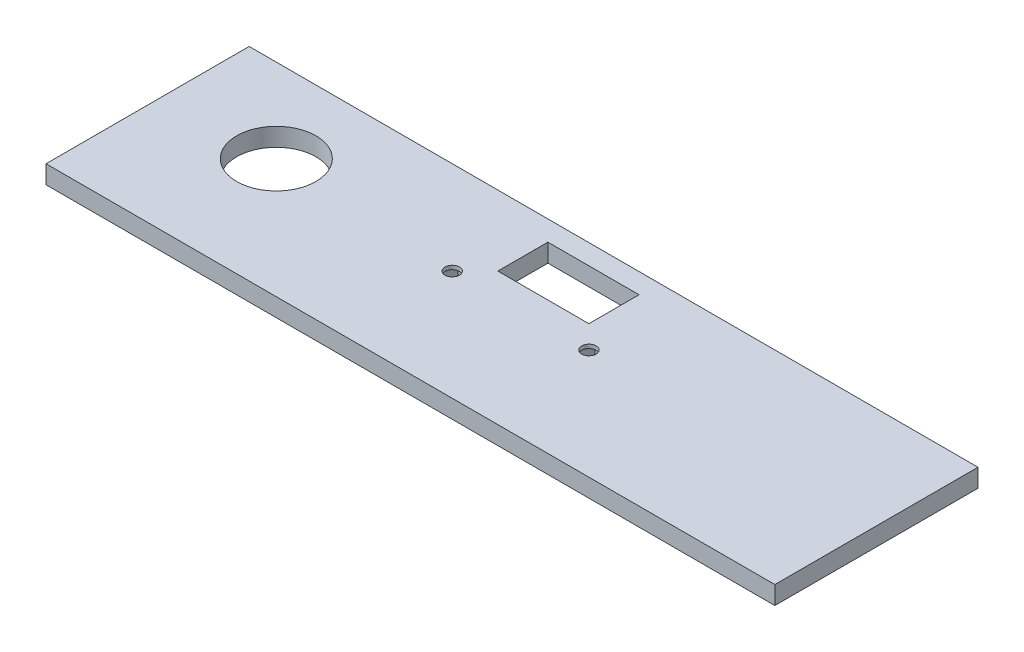
SolidWorks part; units mm, degrees
ref_plane "Front" through (0, 0, 0) normal (0, 0, 1) x (1, 0, 0)
ref_plane "Top" through (0, 0, 0) normal (0, 1, 0) x (1, 0, 0)
ref_plane "Right" through (0, 0, 0) normal (1, 0, 0) x (0, 0, -1)
sketch "Sketch2" plane through (0, 0, 0) normal (0, 1, 0) x (1, 0, 0)
  line L1 (-101.6, 28.321) -> (101.6, 28.321)
  line L2 (-101.6, 28.321) -> (-101.6, -28.321)
  line L3 (-101.6, -28.321) -> (101.6, -28.321)
  line L4 (101.6, 28.321) -> (101.6, -28.321)
  line L5 (-101.6, 28.321) -> (101.6, -28.321) construction
  line L6 (-101.6, -28.321) -> (101.6, 28.321) construction
  line L8 (-70.7277, 5.0127) -> (-70.7277, 16.0617) construction
  line L10 (0, -55) -> (0, 55) construction
  line L11 (-12.7, 22.712) -> (12.7, 22.712)
  line L12 (-12.7, 22.712) -> (-12.7, 8.742)
  line L13 (-12.7, 8.742) -> (12.7, 8.742)
  line L14 (12.7, 22.712) -> (12.7, 8.742)
  line L15 (-12.7, 22.712) -> (12.7, 8.742) construction
  line L16 (-12.7, 8.742) -> (12.7, 22.712) construction
  circle A0 centre (-70.7277, 5.0127) radius 11.049
  circle A1 centre (-19.05, 2.392) radius 2
  circle A2 centre (19.05, 2.392) radius 2
  point P0 (0, 0)
  point P13 (-70.7277, 17.7664)
  point P14 (0, 15.727)
  point P25 (-71.9977, 11.4131)
  dimension "D1" = 22.098
  dimension "D8" = 4
  dimension "D4" = 25.4
  dimension "D5" = 13.97
  dimension "D6" = 203.2
  dimension "D7" = 56.642
  dimension "D9" = 6.35
  dimension "D10" = 19.05
extrude "Boss-Extrude1" add sketch "Sketch2" along normal blind 5.08 contours L4 L1 L2 L3 A0 region at (2.5242, 0, 0.7038)
sketch "Sketch4" plane through (0, 0, 0) normal (0, -1, 0) x (1, 0, 0)
  line L0 (0, -55) -> (0, 55) construction
  line L1 (-16.7695, -6.342) -> (-14.4889, -2.392)
  line L2 (-14.4889, -2.392) -> (-16.7695, 1.558)
  line L3 (-16.7695, 1.558) -> (-21.3305, 1.558)
  line L4 (101.6, -28.321) -> (101.6, 28.321)
  line L5 (101.6, 28.321) -> (-101.6, 28.321)
  line L6 (-101.6, 28.321) -> (-101.6, -28.321)
  line L7 (-101.6, -28.321) -> (101.6, -28.321)
  line L8 (101.6, -28.321) -> (101.6, 28.321)
  line L9 (101.6, 28.321) -> (-101.6, 28.321)
  line L10 (-101.6, 28.321) -> (-101.6, -28.321)
  line L11 (-101.6, -28.321) -> (101.6, -28.321)
  line L12 (-21.3305, 1.558) -> (-23.6111, -2.392)
  line L13 (-23.6111, -2.392) -> (-21.3305, -6.342)
  line L14 (-21.3305, -6.342) -> (-16.7695, -6.342)
  line L15 (16.7695, -6.342) -> (14.4889, -2.392)
  line L16 (21.3305, -6.342) -> (16.7695, -6.342)
  line L17 (23.6111, -2.392) -> (21.3305, -6.342)
  line L18 (21.3305, 1.558) -> (23.6111, -2.392)
  line L19 (16.7695, 1.558) -> (21.3305, 1.558)
  line L20 (14.4889, -2.392) -> (16.7695, 1.558)
  line L21 (101.6, 28.321) -> (101.6, -28.321)
  line L22 (-101.6, -28.321) -> (-101.6, 28.321)
  circle A0 centre (19.05, -2.392) radius 2 construction
  circle A1 centre (-19.05, -2.392) radius 2 construction
  circle A2 centre (19.05, -2.392) radius 2
  circle A3 centre (-19.05, -2.392) radius 2
  circle A4 centre (-19.05, -2.392) radius 3.95 construction
  dimension "D2" = 7.9
  dimension "D1" = 0
extrude "Cut-Extrude1" cut sketch "Sketch4" against normal blind 4 contours L2 L3 L12 L13 L14 L1 | L20 L19 L18 L17 L16 L15
sketch "Sketch5" plane through (0, 0, 28.321) normal (0, 0, 1) x (1, 0, 0)
  line L0 (0, -55) -> (0, 55) construction
  line L1 (-66.675, 5.08) -> (-60.325, 5.08)
  line L2 (-66.675, 5.08) -> (-66.675, -7.62)
  line L3 (-66.675, -7.62) -> (-60.325, -7.62)
  line L4 (-60.325, 5.08) -> (-60.325, -7.62)
  line L5 (66.675, -7.62) -> (60.325, -7.62)
  line L6 (60.325, 5.08) -> (60.325, -7.62)
  line L7 (66.675, 5.08) -> (60.325, 5.08)
  line L8 (-101.6, 0) -> (101.6, 0)
  line L9 (101.6, 0) -> (101.6, 5.08)
  line L10 (101.6, 5.08) -> (-101.6, 5.08)
  line L11 (-101.6, 5.08) -> (-101.6, 0)
  line L12 (-101.6, 0) -> (101.6, 0)
  line L13 (101.6, 0) -> (101.6, 5.08)
  line L14 (101.6, 5.08) -> (-101.6, 5.08)
  line L15 (-101.6, 5.08) -> (-101.6, 0)
  line L16 (66.675, 5.08) -> (66.675, -7.62)
  circle A0 centre (-63.5, -3.81) radius 1.5
  circle A1 centre (63.5, -3.81) radius 1.5
  point P18 (-63.5, -7.62)
  line M13 (-101.6, 0) -> (101.6, 0)
  line M15 (101.6, 5.08) -> (-101.6, 5.08)
  dimension "D4" = 3
  dimension "D2" = 6.35
  dimension "D3" = 12.7
  dimension "D5" = 3.81
  dimension "D6" = 63.5
  dimension "D1" = 0
extrude "Boss-Extrude2" add sketch "Sketch5" along normal blind 3.81 from surface contours L4 L2 L3 A0 M13 | L4 L2 M15 M13 | L16 L6 M15 M13 | L16 L6 L5 A1 M13 region at (-63.5, 2.54, 28.321) region at (-63.5, -0.0992, 28.321) region at (63.5, 2.54, 28.321) region at (63.5, -0.0992, 28.321) starting at face at (0, 2.54, -28.321)
